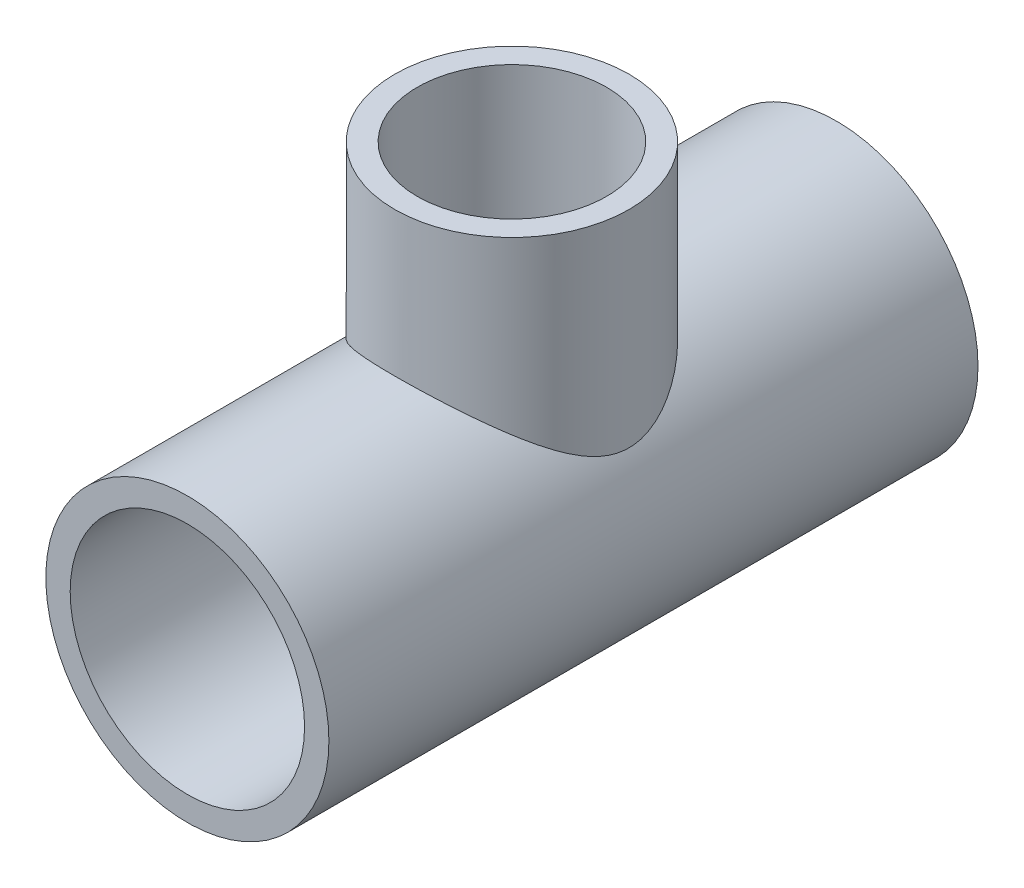
SolidWorks part; units mm, degrees
ref_plane "Front Plane" through (0, 0, 0) normal (0, 0, 1) x (1, 0, 0)
ref_plane "Top Plane" through (0, 0, 0) normal (0, 1, 0) x (1, 0, 0)
ref_plane "Right Plane" through (0, 0, 0) normal (1, 0, 0) x (0, 0, -1)
sketch "Sketch1" plane through (0, 0, 0) normal (0, 0, 1) x (1, 0, 0)
  circle A1 centre (0, 0) radius 19.939
  dimension "D1" = 39.878
extrude "Boss-Extrude1" add sketch "Sketch1" along normal blind 91.44
ref_plane "Plane1" through (0, 0, 45.72) normal (0, 0, 1) x (1, 0, 0)
ref_axis "Axis1" through (0, 55, 45.72) along (0, -1, 0)
ref_plane "Plane2" through (0, 19.939, 0) normal (0, 1, 0) x (1, 0, 0)
sketch "Sketch3" plane through (0, 19.939, 0) normal (0, 1, 0) x (1, 0, 0)
  circle A0 centre (0, -45.72) radius 16.51
  dimension "D1" = 33.02
extrude "Boss-Extrude2" add sketch "Sketch3" along normal blind 20.32 and the other way blind 20.32
sketch "Sketch4" plane through (0, 0, 91.44) normal (0, 0, 1) x (1, 0, 0)
  circle A0 centre (0, 0) radius 16.51
  dimension "D1" = 33.02
extrude "Cut-Extrude1" cut sketch "Sketch4" against normal through all
sketch "Sketch5" plane through (0, 40.259, 0) normal (0, 1, 0) x (1, 0, 0)
  line L0 (-21.9329, -45.72) -> (21.9329, -45.72) construction
  circle A0 centre (0, -45.72) radius 13.335
  dimension "D1" = 26.67
extrude "Cut-Extrude2" cut sketch "Sketch5" against normal up to next
ref_plane "Pipe (1in) #1" through (0, 0, 72.39) normal (0, 0, 1) x (1, 0, 0)
ref_plane "Pipe (3/4in) #1" through (0, 21.209, 0) normal (0, 1, 0) x (1, 0, 0)
ref_plane "Pipe (1in) #2" through (0, 0, 19.05) normal (0, 0, -1) x (-1, 0, 0)
